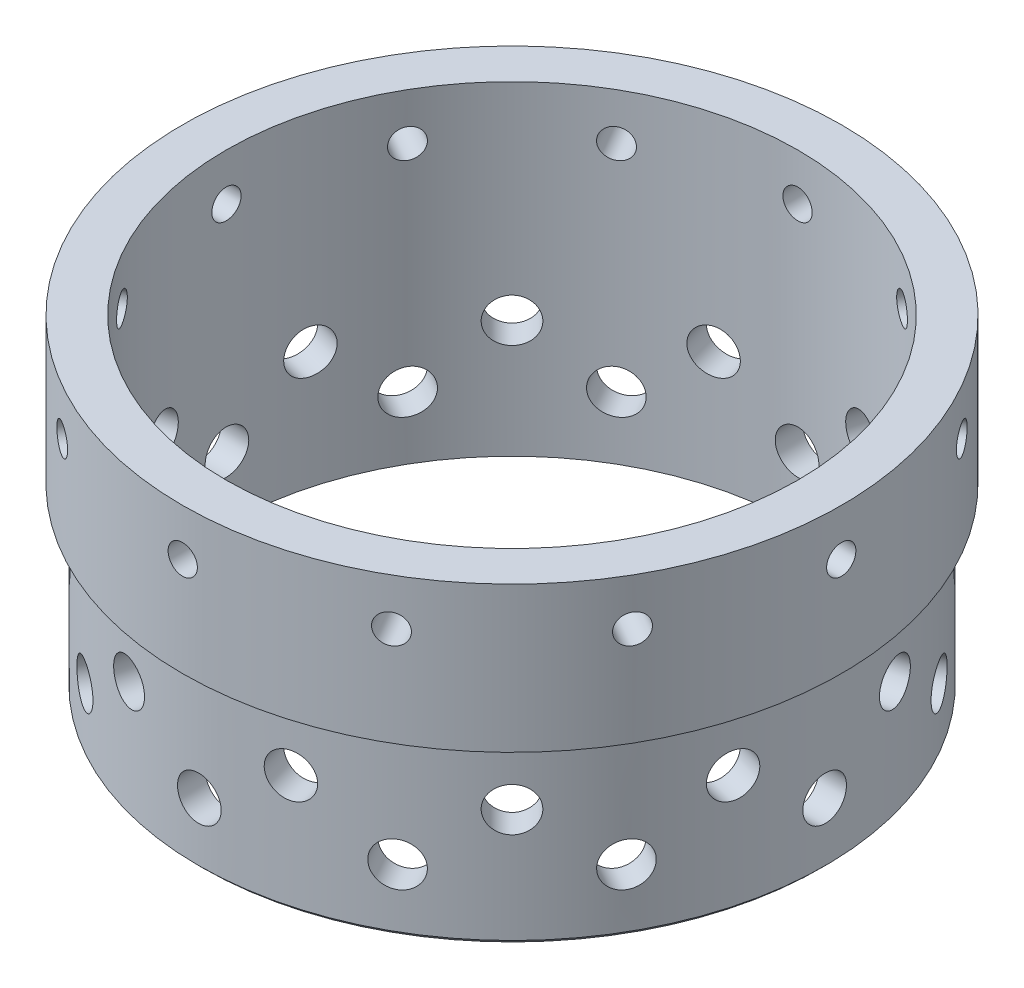
SolidWorks part; units mm, degrees
material "6061-T6 (SS)"
ref_plane "Front Plane" through (0, 0, 0) normal (0, 0, 1) x (1, 0, 0)
ref_plane "Top Plane" through (0, 0, 0) normal (0, 1, 0) x (1, 0, 0)
ref_plane "Right Plane" through (0, 0, 0) normal (1, 0, 0) x (0, 0, -1)
sketch "Sketch1" plane through (0, 0, 0) normal (0, 1, 0) x (1, 0, 0)
  circle A0 centre (0, 0) radius 66.04
  circle A1 centre (0, 0) radius 76.1238
  circle A2 centre (0, 0) radius 72.39
  dimension "D1" = 152.2476
  dimension "D2" = 144.78
  dimension "D3" = 6.35
  dimension "D4" = 10.0838
  dimension "D5" = 144.78
extrude "Boss-Extrude1" add sketch "Sketch1" along normal blind 12.7 contours A2 A0 | A1 A2 region at (-73.9707, 0, 0) region at (-70.3425, 0, 0)
extrude "Boss-Extrude2" add sketch "Sketch1<3>" against normal blind 41.275 contours A2 A0 region at (-70.3425, 0, 0)
sketch "Sketch1<3>" plane through (0, 0, 0) normal (0, 1, 0) x (1, 0, 0) same geometry as "Sketch1"
extrude "Boss-Extrude3" add sketch "Sketch1<4>" along normal blind 33.655 contours A2 A0 | A1 A2 region at (-73.9707, 0, 0) region at (-70.3425, 0, 0)
sketch "Sketch1<4>" plane through (0, 0, 0) normal (0, 1, 0) x (1, 0, 0) same geometry as "Sketch1"
chamfer "Chamfer1" distance 1 angle 45 1 edges at (0, -41.275, 72.39)
sketch "Sketch2" plane through (0, 0, 0) normal (0, 0, 1) x (1, 0, 0)
  line L0 (0, 0) -> (0, 22.86) construction
  line L1 (0, 0) -> (0, -26.797) construction
  line L2 (-71.39, -41.275) -> (71.39, -41.275) construction
  line L4 (76.1238, 33.655) -> (-76.1238, 33.655) construction
  circle A0 centre (0, 22.86) radius 3.3782
  circle A1 centre (0, -26.797) radius 5.0419
  dimension "D1" = 6.7564
  dimension "D2" = 10.0838
  dimension "D3" = 26.797
  dimension "D5" = 14.478
  dimension "D4" = 10.795
extrude "Cut-Extrude1" cut sketch "Sketch2" against normal through all contours A1 region at (0, -26.797, 0)
ref_plane "Plane1" through (-19.7023, 0, 73.5299) normal (-0.2588, 0, 0.9659) x (0, -1, 0)
sketch "Sketch3" plane through (-19.7023, 0, 73.5299) normal (-0.2588, 0, 0.9659) x (0, -1, 0)
  line L0 (14.097, 0) -> (0, 0) construction
  line L1 (41.275, -71.39) -> (41.275, 71.39) construction
  circle A0 centre (14.097, 0) radius 5.0419
  dimension "D1" = 10.0838
  dimension "D2" = 14.097
  dimension "D3" = 27.178
extrude "Cut-Extrude2" cut sketch "Sketch3" against normal blind 38.1
pattern_circular "CirPattern2" count 12 over 360 about axis through (0, 12.7, 0) along (0, -1, 0) of "Cut-Extrude2", "Cut-Extrude1" reverse direction yes
extrude "Cut-Extrude3" cut sketch "Sketch2<3>" against normal through all contours A0
sketch "Sketch2<3>" plane through (0, 0, 0) normal (0, 0, 1) x (1, 0, 0) same geometry as "Sketch2"
pattern_circular "CirPattern3" count 12 over 360 about axis through (0, 12.7, 0) along (0, -1, 0) of "Cut-Extrude3"
fillet "Fillet1" radius 0.4064 1 edges at (0, 0, 72.39)
equation "\"holeDia\"= 0.397in"
equation "\"D2@Sketch2\"=\"holeDia\""
equation "\"numHoles\"=12"
equation "\"D1@Plane1\"=180/\"numHoles\""
equation "\"D1@Sketch3\"=\"holeDia\""
equation "\"D1@CirPattern2\"=\"numHoles\""
